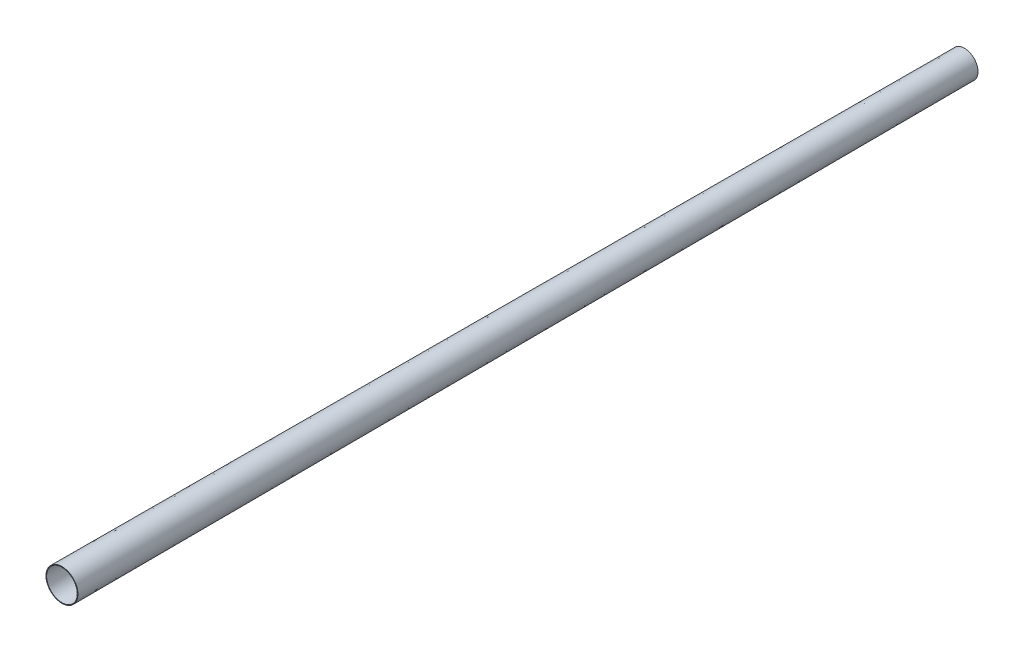
SolidWorks part; units mm, degrees
ref_plane "Front Plane" through (0, 0, 0) normal (0, 0, 1) x (1, 0, 0)
ref_plane "Top Plane" through (0, 0, 0) normal (0, 1, 0) x (1, 0, 0)
ref_plane "Right Plane" through (0, 0, 0) normal (1, 0, 0) x (0, 0, -1)
sketch "Sketch1" plane through (0, 0, 0) normal (0, 0, 1) x (1, 0, 0)
  circle A0 centre (0, 0) radius 9.992
  circle A1 centre (0, 0) radius 10.492
  dimension "D2" = 20.9841
  dimension "D1" = 0.5
ref_plane "Plane1" through (0, 0, 700.9946) normal (0, 0, 1) x (1, 0, 0)
sketch "Sketch2" plane through (0, 0, 700.9946) normal (0, 0, 1) x (1, 0, 0)
  circle A0 centre (0, 0) radius 12.4044
  circle A1 centre (0, 0) radius 11.9044
  dimension "D2" = 24.8088
  dimension "D1" = 0.5
loft "Loft1" add section "Sketch1" section "Sketch2" start constraint default connector at (-9.4907, -4.4733, 0) connector at (-11.2371, -5.2533, 700.9946)
shell "Shell1" thickness 0.5 removed face at (10.492, 0, 0) removed face at (12.4044, 0, 700.9946)
